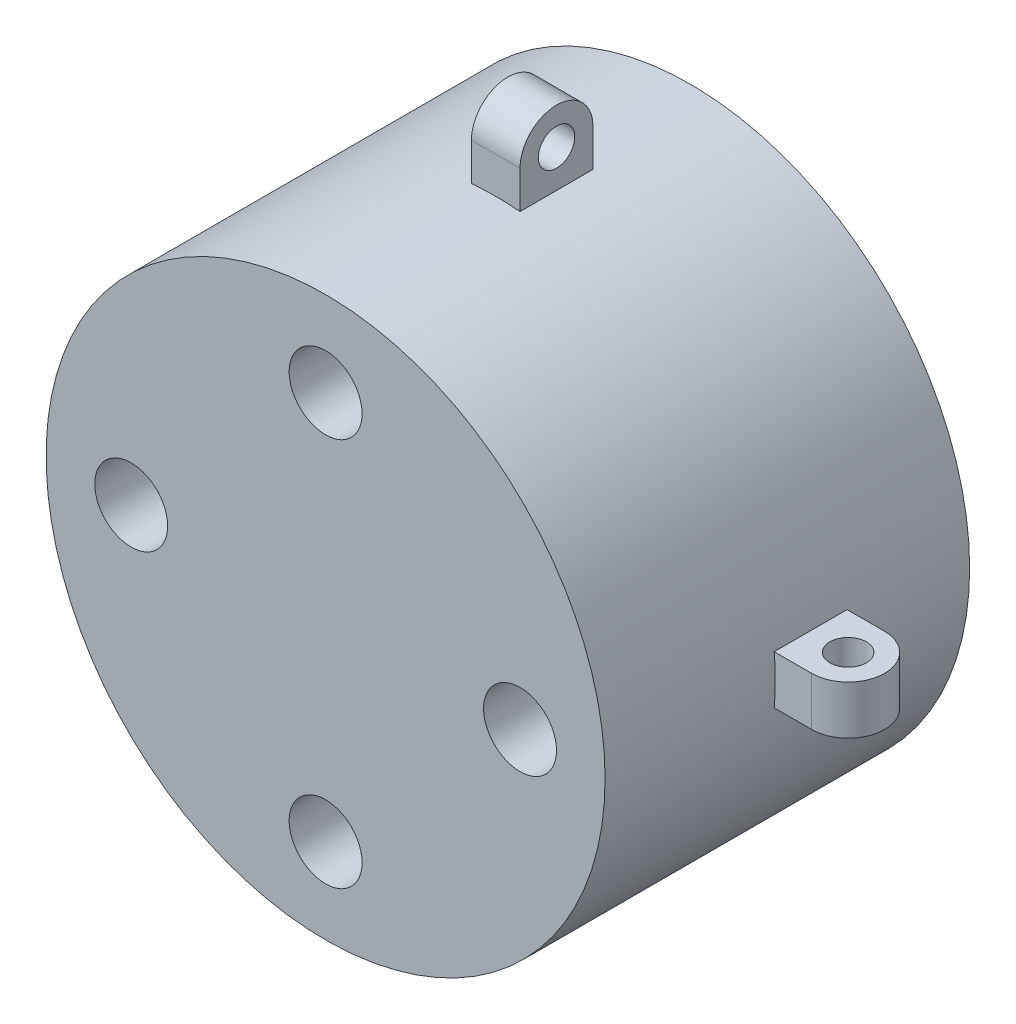
SolidWorks part; units mm, degrees
material "ABS"
ref_plane "前视基准面" through (0, 0, 0) normal (0, 0, 1) x (1, 0, 0)
ref_plane "上视基准面" through (0, 0, 0) normal (0, 1, 0) x (1, 0, 0)
ref_plane "右视基准面" through (0, 0, 0) normal (1, 0, 0) x (0, 0, -1)
sketch "草图1" plane through (0, 0, 0) normal (0, 0, 1) x (1, 0, 0)
  circle A0 centre (0, 0) radius 23
  dimension "D1" = 46
extrude "凸台-拉伸1" add sketch "草图1" along normal blind 30
sketch "草图2" plane through (0, 0, 30) normal (0, 0, 1) x (1, 0, 0)
  line L0 (0, 16) -> (0, 0) construction
  line L1 (0, 0) -> (0, -16) construction
  line L2 (-16, 0) -> (0, 0) construction
  line L3 (0, 0) -> (16, 0) construction
  circle A0 centre (16, 0) radius 3
  circle A1 centre (0, 16) radius 3
  circle A2 centre (-16, 0) radius 3
  circle A3 centre (0, -16) radius 3
  dimension "D1" = 6
  dimension "D2" = 6
  dimension "D7" = 6
  dimension "D8" = 6
  dimension "D3" = 16
  dimension "D4" = 16
  dimension "D5" = 16
  dimension "D6" = 16
extrude "切除-拉伸1" cut sketch "草图2" against normal through all
sketch "草图3" plane through (0, 0, 0) normal (1, 0, 0) x (0, 0, -1)
  line L0 (-10, 22) -> (-16, 22)
  line L1 (-16, 22) -> (-16, 26)
  line L2 (-10, 26) -> (-10, 22)
  line L3 (0, 0) -> (-35.6052, 0) construction
  arc A0 (-16, 26) -> (-10, 26) centre (-13, 26) cw
  dimension "D3" = 3
  dimension "D1" = 22
  dimension "D2" = 4
  dimension "D4" = 10
extrude "凸台-拉伸2" add sketch "草图3" along normal blind 2 and the other way blind 2
sketch "草图4" plane through (2, 0, 0) normal (1, 0, 0) x (0, 0, -1)
  line L0 (-13, 26) -> (-16, 26) construction
  circle A0 centre (-13, 26) radius 1.5
  dimension "D1" = 3
  dimension "D2" = 3
extrude "切除-拉伸2" cut sketch "草图4" against normal through all
pattern_circular "阵列(圆周)2" count 4 every 90 about axis through (0, 0, 30) along (0, 0, -1) of "凸台-拉伸2", "切除-拉伸2"
